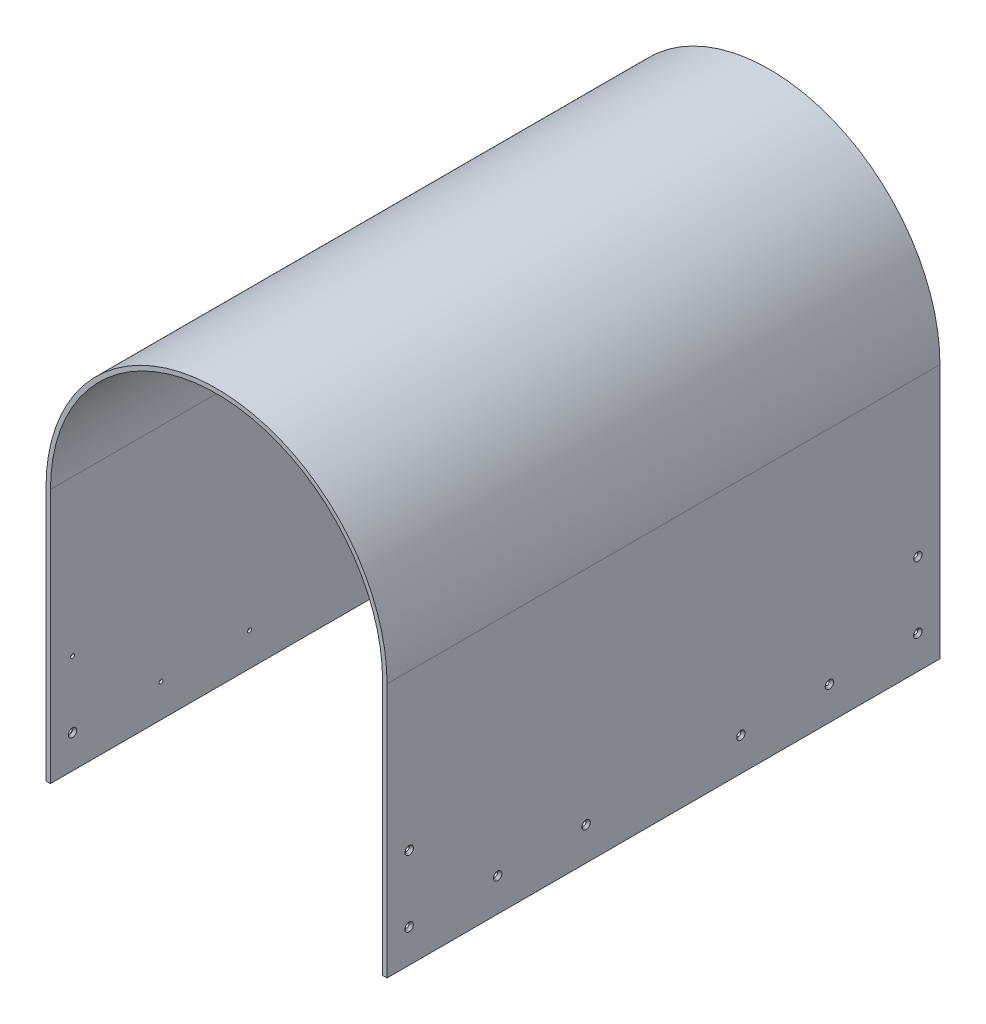
SolidWorks part; units mm, degrees
material "ABS PC"
ref_plane "Front Plane" through (0, 0, 0) normal (0, 0, 1) x (1, 0, 0)
ref_plane "Top Plane" through (0, 0, 0) normal (0, 1, 0) x (1, 0, 0)
ref_plane "Right Plane" through (0, 0, 0) normal (1, 0, 0) x (0, 0, -1)
sketch "Sketch1" plane through (0, 0, 0) normal (0, 0, 1) x (1, 0, 0)
  line L0 (0, 0) -> (0, 212.7728) construction
  line L1 (-75.1, 0) -> (-75.1, 115.2)
  line L2 (75.1, 0) -> (75.1, 115.2)
  line L7 (-26.8281, 0) -> (29.8493, 0) construction
  line L8 (-77.1, 0) -> (-77.1, 115.2)
  line L9 (77.1, 0) -> (77.1, 115.2)
  line L10 (-75.1, 0) -> (-77.1, 0)
  line L11 (75.1, 0) -> (77.1, 0)
  arc A2 (77.1, 115.2) -> (-77.1, 115.2) centre (0, 115.2) ccw
  arc A4 (75.1, 115.2) -> (-75.1, 115.2) centre (0, 115.2) ccw
  dimension "D4" = 75.1
  dimension "D2" = 150.2
  dimension "D3" = 115.2
  dimension "D1" = 2
extrude "Boss-Extrude1" add sketch "Sketch1" along normal mid plane 250
sketch "Sketch3" plane through (-77.1, 0, 0) normal (-1, 0, 0) x (0, 0, 1)
  line L0 (-125, 15) -> (125, 15) construction
  line L1 (-125, 115.2) -> (-125, 0) construction
  line L2 (125, 115.2) -> (125, 0) construction
  line L3 (125, 0) -> (-125, 0) construction
  circle A0 centre (-115, 15) radius 0.9
  circle A1 centre (-75, 15) radius 0.9
  circle A2 centre (-35, 15) radius 0.9
  circle A3 centre (-115, 45) radius 0.9
  dimension "D1" = 15
extrude "Cut-Extrude1" cut sketch "Sketch3" against normal through all
mirror "Mirror1" about plane through (0, 0, 0) normal (0, 0, 1) of "Cut-Extrude1"
chamfer "Chamfer1" distance 1 angle 45 9 edges at (-75.1, 15, 115.9) (-77.1, 15, 114.1) (-77.1, 45, 114.1) (-77.1, 15, 74.1) (-77.1, 15, 34.1) (-77.1, 15, -34.1) (-77.1, 15, -74.1) (-77.1, 15, -114.1) (-77.1, 45, -114.1)
chamfer "Chamfer2" distance 1 angle 45 8 edges at (77.1, 45, -114.1) (77.1, 15, -114.1) (77.1, 15, -74.1) (77.1, 15, -34.1) (77.1, 15, 34.1) (77.1, 15, 74.1) (77.1, 15, 114.1) (77.1, 45, 114.1)
sketch "Sketch4" plane through (-77.1, 0, 0) normal (-1, 0, 0) x (0, 0, 1)
  line L1 (-29, 70) -> (-11, 70)
  line L2 (-29, 70) -> (-29, 84)
  line L3 (-29, 84) -> (-11, 84)
  line L4 (-11, 70) -> (-11, 84)
  line L5 (-29, 70) -> (-11, 84) construction
  line L6 (-29, 84) -> (-11, 70) construction
  point P0 (-20, 77)
extrude "Cut-Extrude2" cut sketch "Sketch4" against normal up to next
